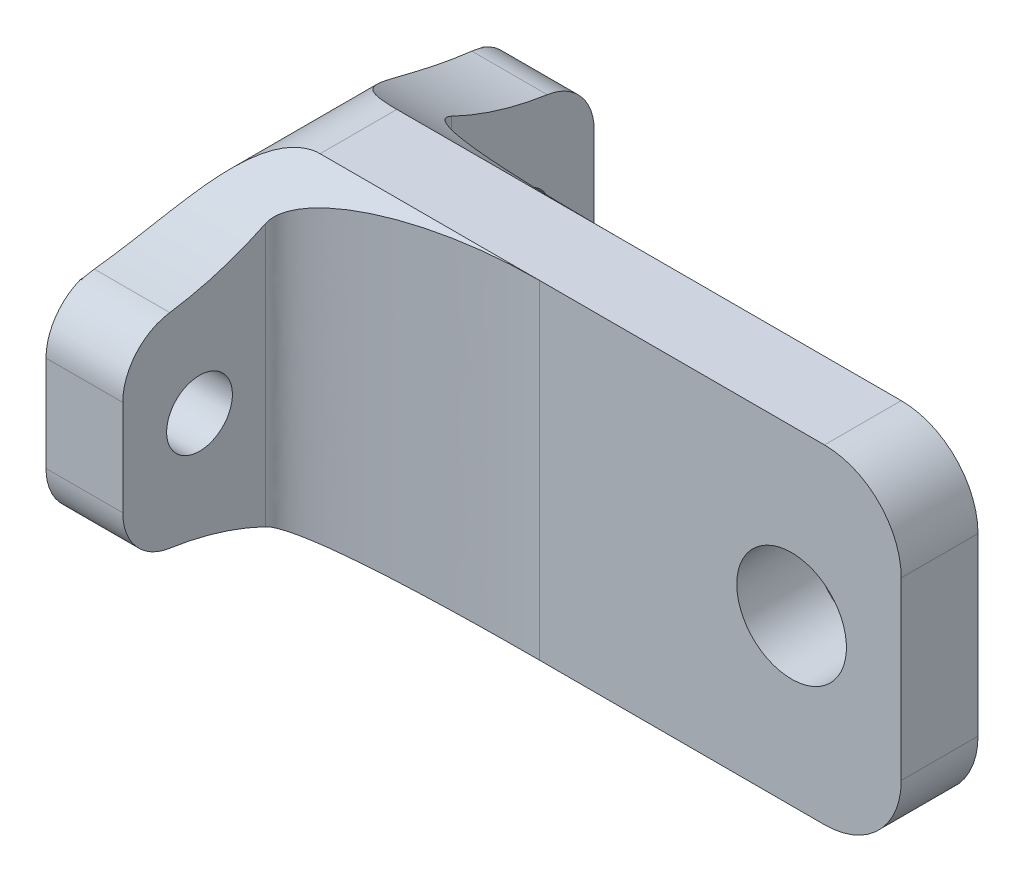
SolidWorks part; units mm, degrees
ref_plane "前视基准面" through (0, 0, 0) normal (0, 0, 1) x (1, 0, 0)
ref_plane "上视基准面" through (0, 0, 0) normal (0, 1, 0) x (1, 0, 0)
ref_plane "右视基准面" through (0, 0, 0) normal (1, 0, 0) x (0, 0, -1)
other "Configuration Table"
sketch "草图1" plane through (0, 0, 0) normal (0, 0, 1) x (1, 0, 0)
  line L1 (0, 0) -> (60, 0)
  line L2 (0, 0) -> (0, 30)
  line L3 (0, 30) -> (60, 30)
  line L4 (60, 0) -> (60, 30)
  dimension "D1" = 30
  dimension "D2" = 60
extrude "凸台-拉伸1" add sketch "草图1" along normal blind 7
sketch "草图2" plane through (0, 0, 0) normal (0, 0, -1) x (-1, 0, 0)
  line L0 (-60, 15) -> (0, 15) construction
  line L1 (-60, 0) -> (-60, 30) construction
  line L2 (0, 30) -> (0, 0) construction
  circle A0 centre (-50, 15) radius 5
  dimension "D1" = 10
  dimension "D2" = 50
extrude "切除-拉伸1" cut sketch "草图2" against normal up to next
fillet "圆角1" radius 7 4 edges at (60, 30, 3.5) (0, 30, 3.5) (0, 0, 3.5) (60, 0, 3.5)
sketch "草图3" plane through (0, 0, 7) normal (0, 0, 1) x (1, 0, 0)
  line L0 (0, 15) -> (20.808, 15) construction
  line L1 (0, 23) -> (0, 7) construction
  line L3 (0, 24) -> (7, 24)
  line L4 (0, 24) -> (0, 6)
  line L5 (0, 6) -> (7, 6)
  line L6 (7, 24) -> (7, 6)
  dimension "D1" = 18
  dimension "D2" = 9
  dimension "D3" = 7
extrude "凸台-拉伸2" add sketch "草图3" along normal blind 18
sketch "草图4" plane through (0, 0, 0) normal (0, 0, -1) x (-1, 0, 0)
  line L0 (0, 15) -> (-18.6209, 15) construction
  line L1 (0, 23) -> (0, 7) construction
  line L7 (0, 24) -> (-7, 24)
  line L8 (0, 24) -> (0, 6)
  line L9 (0, 6) -> (-7, 6)
  line L10 (-7, 24) -> (-7, 6)
  dimension "D1" = 18
  dimension "D2" = 9
  dimension "D3" = 7
extrude "凸台-拉伸3" add sketch "草图4" along normal blind 18
sketch "草图5" plane through (0, 0, 0) normal (-1, 0, 0) x (0, 0, 1)
  line L0 (-18, 15) -> (25, 15) construction
  line L1 (-18, 6) -> (-18, 24) construction
  line L2 (25, 24) -> (25, 6) construction
  circle A0 centre (-11, 15) radius 3
  circle A1 centre (18, 15) radius 3
  dimension "D1" = 6
  dimension "D2" = 6
  dimension "D3" = 7
  dimension "D4" = 7
extrude "切除-拉伸2" cut sketch "草图5" against normal up to next
fillet "圆角2" radius 20 2 edges at (7, 15, 7) (7, 15, 0)
fillet "圆角3" radius 30 4 edges
fillet "圆角4" radius 5 3 edges at (0.0359, 24, 25) (2.4099, 28.2849, 9.5489) (3.5359, 24, 25)
fillet "圆角5" radius 5 3 edges at (3.5359, 6, 25) (0.0359, 6, 25)
fillet "圆角6" radius 5 3 edges at (0.0359, 6, -18) (2.4099, 1.7151, -2.5489) (3.5359, 6, -18)
fillet "圆角7" radius 5 3 edges at (3.5359, 24, -18) (0.0359, 24, -18)
